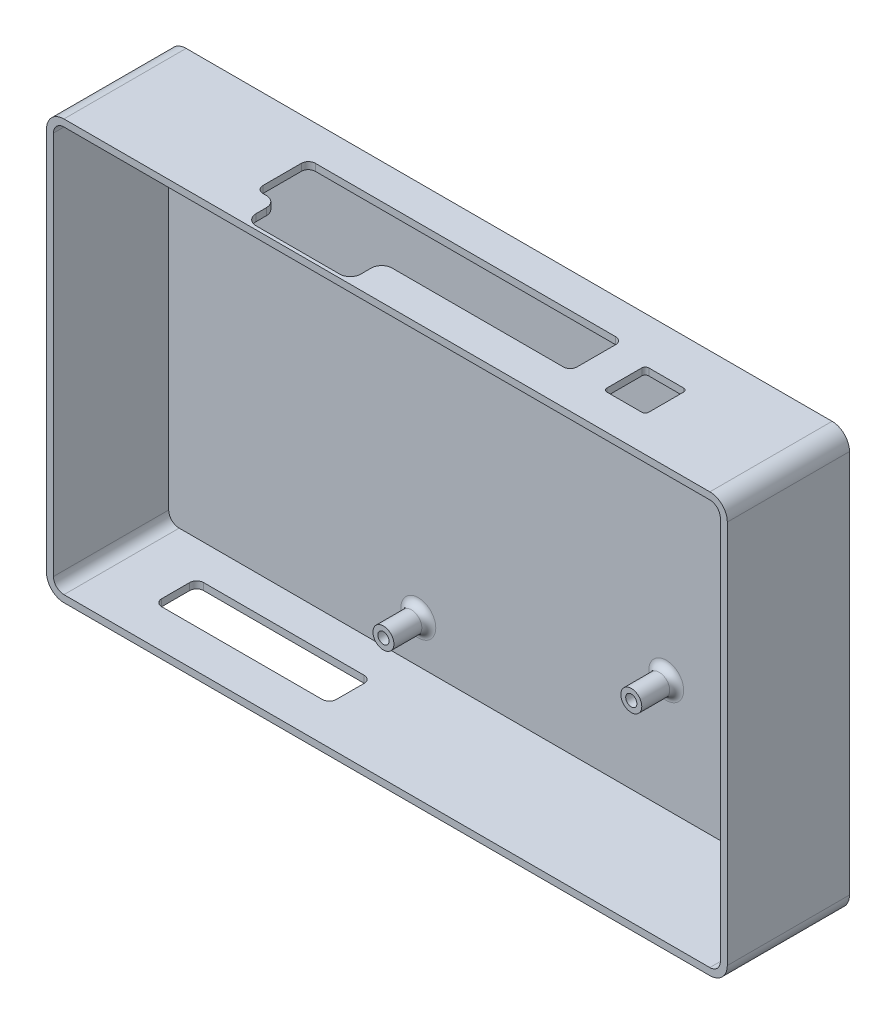
SolidWorks part; units mm, degrees
ref_plane "Plan de face" through (0, 0, 0) normal (0, 0, 1) x (1, 0, 0)
ref_plane "Plan de dessus" through (0, 0, 0) normal (0, 1, 0) x (1, 0, 0)
ref_plane "Plan de droite" through (0, 0, 0) normal (1, 0, 0) x (0, 0, -1)
sketch "Esquisse1" plane through (0, 0, 0) normal (0, 0, 1) x (1, 0, 0)
  line L1 (5, 0) -> (190, 0)
  line L2 (0, 5) -> (0, 115)
  line L3 (5, 120) -> (190, 120)
  line L4 (195, 5) -> (195, 115)
  line L5 (0, 0) -> (195, 120) construction
  line L6 (0, 120) -> (195, 0) construction
  arc A0 (190, 0) -> (195, 5) centre (190, 5) ccw
  arc A1 (0, 115) -> (5, 120) centre (5, 115) cw
  arc A2 (190, 120) -> (195, 115) centre (190, 115) cw
  arc A3 (5, 0) -> (0, 5) centre (5, 5) cw
  point P4 (97.5, 60)
  dimension "D3" = 5
  dimension "D1" = 195
  dimension "D2" = 120
extrude "Boss.-Extru.1" add sketch "Esquisse1" along normal blind 35
shell "Coque1" thickness 2 removed face at (97.5, 60, 35)
sketch "Esquisse2" plane through (0, 120, 0) normal (0, 1, 0) x (1, 0, 0)
  line L1 (149.5, -13) -> (161.5, -13)
  line L2 (149.5, -13) -> (149.5, -25)
  line L3 (149.5, -25) -> (161.5, -25)
  line L4 (161.5, -13) -> (161.5, -25)
  line L5 (149.5, -13) -> (161.5, -25) construction
  line L6 (149.5, -25) -> (161.5, -13) construction
  line L11 (52, -10) -> (138, -10)
  line L12 (50, -12) -> (50, -23)
  line L13 (52, -25) -> (138, -25)
  line L14 (140, -12) -> (140, -23)
  line L15 (50, -10) -> (140, -25) construction
  line L16 (50, -25) -> (140, -10) construction
  line L19 (190, 0) -> (5, 0) construction
  line L20 (190, -35) -> (190, 0) construction
  arc A0 (138, -10) -> (140, -12) centre (138, -12) cw
  arc A1 (50, -23) -> (52, -25) centre (52, -23) ccw
  arc A2 (138, -25) -> (140, -23) centre (138, -23) ccw
  arc A3 (52, -10) -> (50, -12) centre (52, -12) ccw
  point P4 (155.5, -19)
  point P10 (95, -17.5)
  dimension "D1" = 2
  dimension "D2" = 90
  dimension "D3" = 10
  dimension "D4" = 15
  dimension "D5" = 9.5
  dimension "D6" = 12
  dimension "D7" = 12
  dimension "D8" = 13
  dimension "D9" = 28.5
extrude "Enlèv. mat.-Extru.1" cut sketch "Esquisse2" against normal blind 10
sketch "Esquisse3" plane through (0, 120, 0) normal (0, 1, 0) x (1, 0, 0)
  line L0 (52, -25) -> (138, -25) construction
  line L1 (56, -25) -> (86, -25)
  line L2 (56, -25) -> (56, -34)
  line L3 (56, -34) -> (86, -34)
  line L4 (86, -25) -> (86, -34)
  line L5 (56, -25) -> (86, -34) construction
  line L6 (56, -34) -> (86, -25) construction
  line L7 (50, -12) -> (50, -23) construction
  point P4 (71, -29.5)
  dimension "D1" = 9
  dimension "D2" = 30
  dimension "D3" = 6
extrude "Enlèv. mat.-Extru.2" cut sketch "Esquisse3" against normal blind 10
sketch "Esquisse4" plane through (0, 0, 0) normal (0, -1, 0) x (1, 0, 0)
  line L0 (5, 0) -> (190, 0) construction
  line L1 (20, 24) -> (70, 24)
  line L2 (20, 24) -> (20, 12)
  line L3 (20, 12) -> (70, 12)
  line L4 (70, 24) -> (70, 12)
  line L5 (20, 24) -> (70, 12) construction
  line L6 (20, 12) -> (70, 24) construction
  line L7 (5, 35) -> (5, 0) construction
  point P4 (45, 18)
  dimension "D1" = 12
  dimension "D2" = 12
  dimension "D3" = 15
  dimension "D4" = 50
extrude "Enlèv. mat.-Extru.3" cut sketch "Esquisse4" against normal blind 10
fillet "Congé1" radius 3 4 edges at (56, 119, 34) (86, 119, 34) (56, 119, 25) (86, 119, 25)
fillet "Congé2" radius 1 4 edges at (161.5, 119, 13) (161.5, 119, 25) (149.5, 119, 13) (149.5, 119, 25)
fillet "Congé3" radius 2 4 edges at (70, 1, 12) (70, 1, 24) (20, 1, 24) (20, 1, 12)
sketch "Esquisse5" plane through (0, 0, 2) normal (0, 0, 1) x (1, 0, 0)
  circle A0 centre (10.5, 113) radius 3
  circle A1 centre (73.5, 14) radius 3
  circle A2 centre (144.5, 34) radius 3
  circle A3 centre (183.5, 112) radius 3
  circle A4 centre (183.5, 112) radius 1.6
  circle A5 centre (73.5, 14) radius 1.6
  circle A6 centre (144.5, 34) radius 1.6
  circle A7 centre (10.5, 113) radius 1.6
  dimension "D1" = 6
  dimension "D2" = 1.4
  dimension "D3" = 1.4
  dimension "D4" = 1.4
  dimension "D5" = 1.4
extrude "Boss.-Extru.2" add sketch "Esquisse5" along normal blind 10
fillet "Congé4" radius 2 4 edges at (76.5, 14, 2) (147.5, 34, 2) (186.5, 112, 2) (13.5, 113, 2)
